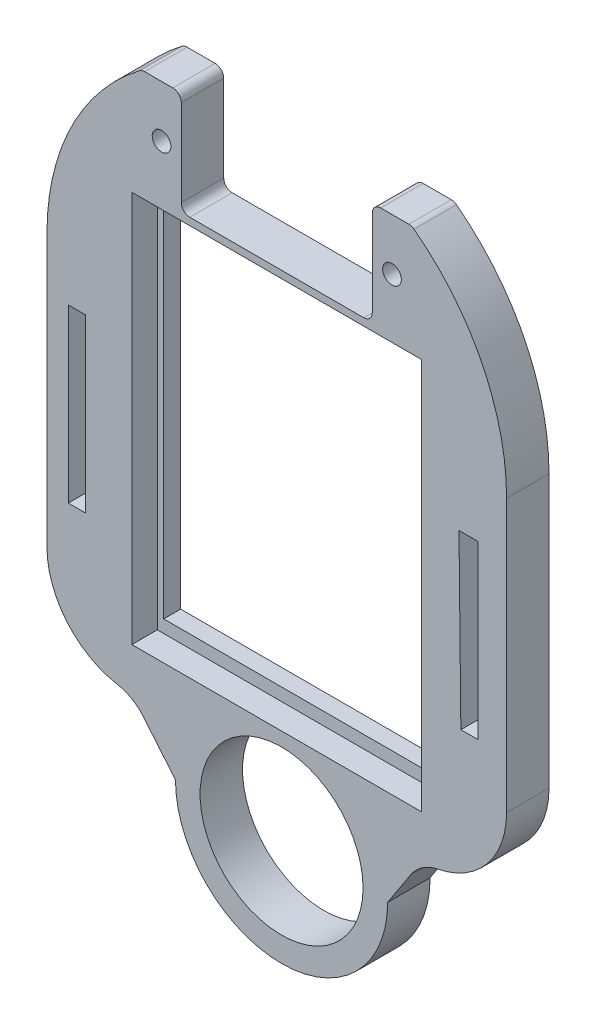
SolidWorks part; units mm, degrees
ref_plane "Plan de face" through (0, 0, 0) normal (0, 0, 1) x (1, 0, 0)
ref_plane "Plan de dessus" through (0, 0, 0) normal (0, 1, 0) x (1, 0, 0)
ref_plane "Plan de droite" through (0, 0, 0) normal (1, 0, 0) x (0, 0, -1)
sketch "Esquisse1" plane through (0, 0, 0) normal (0, 0, 1) x (1, 0, 0)
  line L8 (-20.2431, 24.4782) -> (-20.2431, -25.5218)
  line L9 (-10.2431, 22.5532) -> (23.9069, 22.5532) construction
  line L10 (-10.2431, 22.5532) -> (-10.2431, -23.5968) construction
  line L11 (-10.2431, -23.5968) -> (23.9069, -23.5968) construction
  line L12 (23.9069, 22.5532) -> (23.9069, -23.5968) construction
  line L15 (6.8319, 24.7461) -> (6.8319, -25.5968) construction
  line L20 (33.9069, 24.4782) -> (33.9069, -25.5218)
  line L27 (22.2069, 21.2482) -> (22.2069, -22.1018)
  line L28 (22.2069, 21.2482) -> (-9.4931, 21.2482)
  line L29 (-9.4931, 21.2482) -> (-9.4931, -22.1018)
  line L30 (22.2069, -22.1018) -> (-9.4931, -22.1018)
  line L35 (-20.2431, -25.5218) -> (-20.2431, -25.5968)
  line L38 (33.9069, -25.5968) -> (33.9069, -25.5218)
  line L40 (5.8319, 26.4782) -> (33.9069, 26.4782)
  line L41 (33.9069, 26.4782) -> (33.9069, 24.4782)
  line L42 (5.8319, 26.4782) -> (-20.2431, 26.4782)
  line L43 (-20.2431, 26.4782) -> (-20.2431, 24.4782)
  line L44 (6.8319, -25.5968) -> (33.9069, -25.5968)
  line L45 (6.8319, -25.5968) -> (-20.2431, -25.5968)
  point P0 (5.8319, 26.4782)
  point P5 (-20.2431, -0.5218)
  point P6 (-10.2431, -0.5218)
  point P18 (6.8319, -25.5968)
  dimension "D1" = 50
  dimension "D2" = 0
  dimension "D3" = 34.15
  dimension "D4" = 46.15
  dimension "D5" = 10
  dimension "D6" = 10
  dimension "D7" = 2
  dimension "D8" = 2
extrude "Boss.-Extru.1" add sketch "Esquisse1" along normal blind 2
sketch "Esquisse2" plane through (0, 0, 2) normal (0, 0, 1) x (1, 0, 0)
  line L8 (-11.1931, -23.4068) -> (-11.1931, 22.7432)
  line L9 (-11.1931, -23.4068) -> (22.9569, -23.4068)
  line L10 (22.9569, -23.4068) -> (22.9569, 22.7432)
  line L11 (-11.1931, 22.7432) -> (22.9569, 22.7432)
  line L22 (-20.2431, 26.4782) -> (-20.2431, -25.5968)
  line L23 (-20.2431, -25.5968) -> (33.9069, -25.5968)
  line L24 (33.9069, -25.5968) -> (33.9069, 26.4782)
  line L25 (33.9069, 26.4782) -> (-20.2431, 26.4782)
  point P12 (22.2069, -22.1018)
extrude "Boss.-Extru.2" add sketch "Esquisse2" along normal blind 3
sketch "Esquisse3" plane through (0, 0, 5) normal (0, 0, 1) x (1, 0, 0)
  line L5 (-17.7305, -9.8391) -> (-17.7305, 10.3809)
  line L6 (-17.7305, -9.8391) -> (-15.7305, -9.8391)
  line L7 (-15.7305, -9.8391) -> (-15.5105, 10.3797)
  line L8 (-17.7305, 10.3809) -> (-15.5105, 10.3797)
  line L9 (6.3945, -41.8391) -> (6.3945, 42.1609) construction
  line L10 (28.5195, -9.8391) -> (28.2995, 10.3797)
  line L11 (30.5195, 10.3809) -> (28.2995, 10.3797)
  line L12 (30.5195, -9.8391) -> (30.5195, 10.3809)
  line L13 (30.5195, -9.8391) -> (28.5195, -9.8391)
  dimension "D1" = 20.22
  dimension "D2" = 2.22
extrude "Enlèv. mat.-Extru.1" cut sketch "Esquisse3" against normal through all
fillet "Congé1" radius 10 4 edges at (33.9069, 26.4782, 2.5) (33.9069, -25.5968, 2.5) (-20.2431, -25.5968, 2.5) (-20.2431, 26.4782, 2.5)
sketch "Esquisse4" plane through (0, 0, 0) normal (0, 0, 1) x (1, 0, 0)
  line L12 (-9.0681, 38.6782) -> (-4.4181, 38.6782)
  line L13 (-4.4181, 38.6782) -> (-4.4181, 26.4782)
  line L16 (-6.7431, 38.6782) -> (-6.7431, 26.4782) construction
  line L17 (-9.0681, 32.5782) -> (-4.4181, 32.5782) construction
  line L18 (23.9069, 26.4782) -> (-10.2431, 26.4782) construction
  line L19 (-20.2431, 16.4782) -> (-20.2431, -15.5968)
  line L20 (6.8319, 26.4782) -> (6.8319, 41.5577) construction
  line L22 (22.7319, 32.5782) -> (18.0819, 32.5782) construction
  line L23 (20.4069, 38.6782) -> (20.4069, 26.4782) construction
  line L25 (22.7319, 38.6782) -> (18.0819, 38.6782)
  line L26 (18.0819, 38.6782) -> (18.0819, 26.4782)
  line L29 (-4.4181, 26.4782) -> (18.0819, 26.4782)
  line L31 (-5.1045, -31.7597) -> (-10.2431, -25.5968)
  line L32 (19.8955, -31.7597) -> (23.9069, -25.5968)
  line L33 (33.9069, 16.4782) -> (33.9069, -15.5968)
  line L35 (-17.7305, 10.3809) -> (-15.7305, 10.3809)
  line L36 (-17.7305, 10.3809) -> (-17.7305, -9.8391)
  line L37 (-17.7305, -9.8391) -> (-15.7305, -9.8391)
  line L38 (-15.7305, 10.3809) -> (-15.7305, -9.8391)
  line L39 (28.2995, 10.3797) -> (30.5195, 10.3797)
  line L40 (28.2995, 10.3797) -> (28.2995, -9.8391)
  line L41 (28.2995, -9.8391) -> (30.5195, -9.8391)
  line L42 (30.5195, 10.3797) -> (30.5195, -9.8391)
  circle A2 centre (-6.7431, 32.5782) radius 1.1
  circle A3 centre (20.4069, 32.5782) radius 1.1
  arc A5 (-5.1045, -31.7597) -> (19.8955, -31.7597) centre (7.3955, -31.7597) ccw
  arc A6 (-20.2431, -15.5968) -> (-10.2431, -25.5968) centre (-10.2431, -15.5968) ccw
  arc A9 (33.9069, -15.5968) -> (23.9069, -25.5968) centre (23.9069, -15.5968) cw
  arc A10 (-20.2431, 16.4782) -> (-9.0681, 38.6782) centre (7.3955, 16.4782) cw
  arc A11 (33.9069, 16.4782) -> (22.7319, 38.6782) centre (6.2684, 16.4782) ccw
  dimension "D3" = 2.2
  dimension "D6" = 25
  dimension "D1" = 4.65
  dimension "D4" = 11.25
extrude "Boss.-Extru.3" add sketch "Esquisse4" along normal blind 5
fillet "Congé2" radius 1 6 edges at (-4.4181, 26.4782, 2.5) (18.0819, 38.6782, 2.5) (-4.4181, 38.6782, 2.5) (18.0819, 26.4782, 2.5) (22.7319, 38.6782, 2.5) (-9.0681, 38.6782, 2.5)
fillet "Congé3" radius 5 2 edges at (-10.2431, -25.5968, 2.5) (23.9069, -25.5968, 2.5)
sketch "Esquisse5" plane through (0, 0, 5) normal (0, 0, 1) x (1, 0, 0)
  circle A0 centre (7.3955, -31.7597) radius 9.6
  dimension "D1" = 19.2
extrude "Enlèv. mat.-Extru.2" cut sketch "Esquisse5" against normal through all
sketch "Esquisse7" plane through (0, 0, 5) normal (0, 0, 1) x (1, 0, 0)
  line L0 (-10.2431, 25.617) -> (23.9069, 25.617)
  line L1 (-10.2431, 25.617) -> (-10.2431, -20.533)
  line L2 (-10.2431, -20.533) -> (23.9069, -20.533)
  line L3 (23.9069, 25.617) -> (23.9069, -20.533)
  line L4 (22.2069, 24.312) -> (22.2069, -19.038)
  line L5 (22.2069, 24.312) -> (-9.4931, 24.312)
  line L6 (-9.4931, 24.312) -> (-9.4931, -19.038)
  line L7 (22.2069, -19.038) -> (-9.4931, -19.038)
  line L8 (-20.2431, 0.4407) -> (33.9069, 0.4407) construction
  line L9 (-20.2431, 16.4782) -> (-20.2431, -15.5968) construction
  line L10 (33.9069, -15.5968) -> (33.9069, 16.4782) construction
  line L11 (6.8319, 0.4407) -> (6.8319, 37.8323) construction
  point P0 (-10.2431, 2.542)
extrude "Enlèv. mat.-Extru.3" cut sketch "Esquisse7" against normal through all contours L5 L6 L7 L4
extrude "Enlèv. mat.-Extru.4" cut sketch "Esquisse7<4>" against normal blind 3 contours L0 L3 L2 L1
sketch "Esquisse7<4>" plane through (0, 0, 5) normal (0, 0, 1) x (1, 0, 0) same geometry as "Esquisse7"
